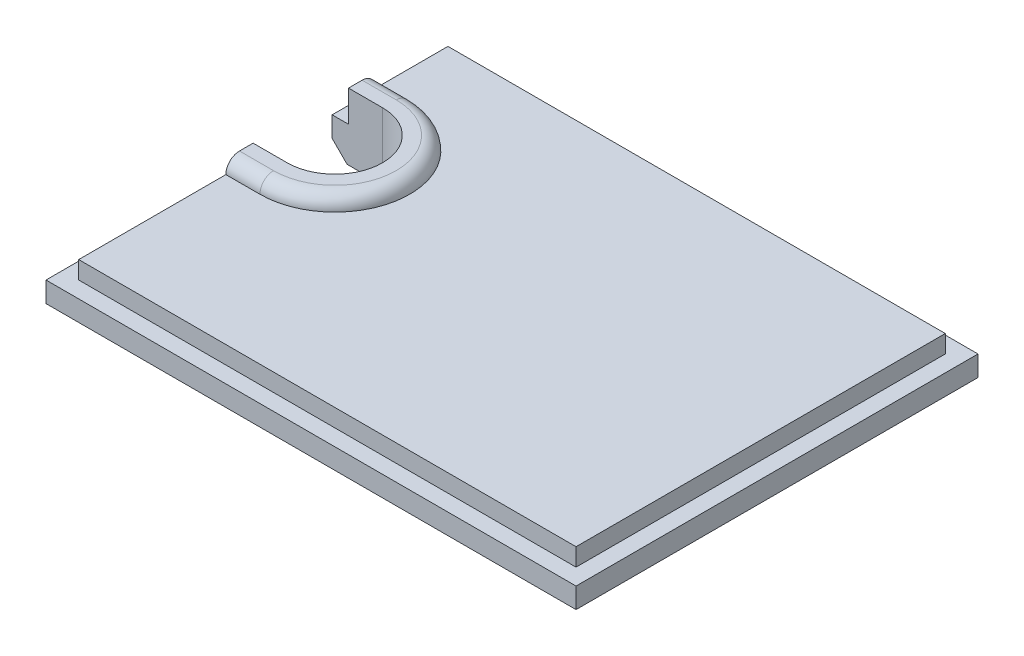
SolidWorks part; units mm, degrees
ref_plane "Front Plane" through (0, 0, 0) normal (0, 0, 1) x (1, 0, 0)
ref_plane "Top Plane" through (0, 0, 0) normal (0, 1, 0) x (1, 0, 0)
ref_plane "Right Plane" through (0, 0, 0) normal (1, 0, 0) x (0, 0, -1)
sketch "Sketch1" plane through (0, 0, 0) normal (0, 1, 0) x (1, 0, 0)
  line L0 (-19.45, 14.75) -> (-19.45, 6.25)
  line L1 (-19.45, -14.75) -> (19.45, -14.75)
  line L2 (19.45, -14.75) -> (19.45, 14.75)
  line L3 (19.45, 14.75) -> (-19.45, 14.75)
  line L4 (18.25, 13.55) -> (-18.25, 13.55)
  line L5 (-18.25, 13.55) -> (-18.25, 6.25)
  line L6 (-18.25, -13.55) -> (18.25, -13.55)
  line L7 (18.25, -13.55) -> (18.25, 13.55)
  line L8 (-18.25, 13.55) -> (0, 0) construction
  line L9 (0, 0) -> (18.25, -13.55) construction
  line L10 (0, 0) -> (18.25, 13.55) construction
  line L11 (0, 0) -> (-18.25, -13.55) construction
  line L12 (-15.75, 8.25) -> (-18.25, 8.25)
  line L13 (-18.25, 8.25) -> (-19.45, 8.25)
  line L14 (-15.75, 6.25) -> (-18.25, 6.25)
  line L15 (-18.25, 6.25) -> (-19.45, 6.25)
  line L16 (-15.75, -0.75) -> (-18.25, -0.75)
  line L17 (-18.25, -0.75) -> (-19.45, -0.75)
  line L18 (-15.75, -2.75) -> (-18.25, -2.75)
  line L19 (-18.25, -2.75) -> (-19.45, -2.75)
  line L20 (-19.45, -0.75) -> (-19.45, -14.75)
  line L21 (-19.45, 14.75) -> (-19.45, -14.75) construction
  line L22 (-18.25, -0.75) -> (-18.25, -13.55)
  line L23 (-18.25, 13.55) -> (-18.25, -13.55) construction
  arc A0 (-15.75, 6.25) -> (-15.75, -0.75) centre (-15.75, 2.75) cw
  arc A1 (-15.75, 8.25) -> (-15.75, -2.75) centre (-15.75, 2.75) cw
  arc A2 (-17.6698, 5.6765) -> (-15.75, -0.75) centre (-15.75, 2.75) cw construction
  arc A3 (-18.7669, 7.3487) -> (-15.75, -2.75) centre (-15.75, 2.75) cw construction
  dimension "D4" = 3.5
  dimension "D6" = 2
  dimension "D1" = 29.5
  dimension "D2" = 38.9
  dimension "D5" = 12
  dimension "D7" = 2.5
  dimension "D3" = 1.2
extrude "Boss-Extrude1" add sketch "Sketch1" along normal blind 1 contours L12 A1 L18 L5 L6 L7 L4 | A1 L12 L5 L14 A0 L16 L18 | L19 L5 L17 L0 | L15 L5 L13 L0 | L5 L19 L0 L1 L2 L3 L13 L4 L7 L6 | L17 L20 L1 L2 L3 L0 L15 L14 A0 L16 | L4 L5 L6 L7 region at (0, 0, -14.2618) region at (-18.85, 0, -7.25) region at (-17, 0, -8.114) region at (1.2088, 0, 0.2257) region at (-18.85, 0, 1.75)
extrude "Boss-Extrude2" add sketch "Sketch1<5>" along normal blind 1.6 from surface contours L5 A1 L6 L7 L4 | A1 L5 A0 | A1 L0 A0 L5 | L0 A1 L5 L4 L7 L6 L1 L2 L3 | A1 L5 A0 L0 | L5 L0 | L5 L0 | L22 L17 L20 L19 region at (0, 0, -14.2618) region at (-18.85, 0, -7.25) region at (-17, 0, -8.114) region at (1.2088, 0, 0.2257) region at (-18.85, 0, 1.75) starting at face at (-8.3625, 1, -1.375)
sketch "Sketch1<5>" plane through (0, 0, 0) normal (0, 1, 0) x (1, 0, 0) same geometry as "Sketch1"
extrude "Boss-Extrude3" add sketch "Sketch1<6>" along normal blind 1.3 from surface contours L5 A1 L6 L7 L4 | A1 L5 A0 region at (-17, 0, -8.114) region at (1.2088, 0, 0.2257) starting at face at (-8.3625, 2.6, -1.375)
sketch "Sketch1<6>" plane through (0, 0, 0) normal (0, 1, 0) x (1, 0, 0) same geometry as "Sketch1"
extrude "Boss-Extrude4" add sketch "Sketch1<8>" along normal blind 1 from surface contours A1 L5 A0 region at (-17, 0, -8.114) starting at face at (-8.0625, 3.9, -1.375)
sketch "Sketch1<8>" plane through (0, 0, 0) normal (0, 1, 0) x (1, 0, 0) same geometry as "Sketch1"
fillet "Fillet1" radius 1 3 edges at (-10.25, 4.9, -2.75) (-17, 4.9, 2.75) (-17, 4.9, -8.25)
chamfer "Chamfer1" distance 1.1 angle 45 4 edges at (0, 0, -14.75) (19.45, 0, 0) (0, 0, 14.75) (-19.45, 0, -10.5)
